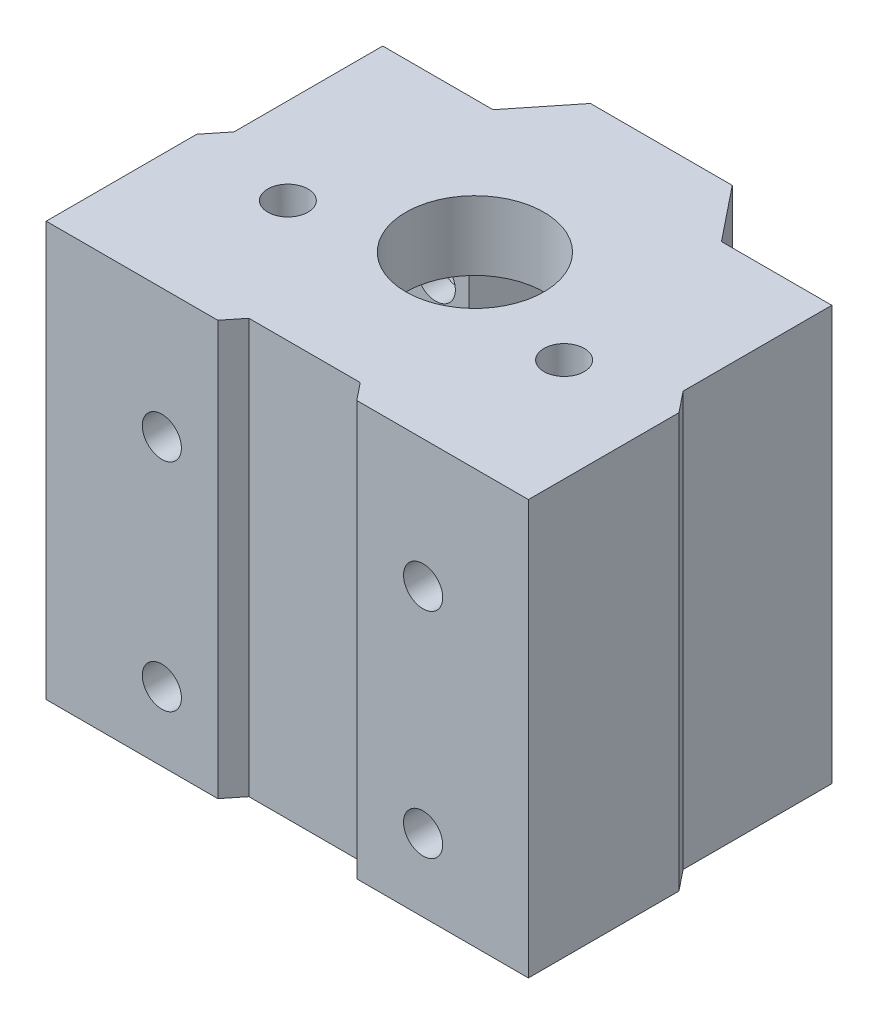
SolidWorks part; units mm, degrees
note: The reader was unsure of these and kept them because the rebuilt part matched: shared geometry of "Sketch2<3>".
ref_plane "Front Plane" through (0, 0, 0) normal (0, 0, 1) x (1, 0, 0)
ref_plane "Top Plane" through (0, 0, 0) normal (0, 1, 0) x (1, 0, 0)
ref_plane "Right Plane" through (0, 0, 0) normal (1, 0, 0) x (0, 0, -1)
sketch "Sketch1" plane through (0, 0, 0) normal (0, 1, 0) x (1, 0, 0)
  line L0 (-22.4581, 3.168) -> (18.1635, 3.168) construction
  line L19 (-4, 11.7) -> (4, 11.7)
  line L20 (4, 11.7) -> (7.76, 7)
  line L21 (7.76, 7) -> (15.01, 7)
  line L22 (15.01, 7) -> (15.01, -3)
  line L23 (15.01, -3) -> (16.45, -4.8)
  line L24 (16.45, -4.8) -> (16.45, -11.8)
  line L25 (16.45, -11.8) -> (8.2, -11.8)
  line L26 (8.2, -11.8) -> (7, -10.3)
  line L27 (7, -10.3) -> (-7, -10.3)
  line L28 (0, 11.7) -> (0, -10.3) construction
  line L29 (-8.2, -11.8) -> (-7, -10.3)
  line L30 (-16.45, -11.8) -> (-8.2, -11.8)
  line L31 (-15.01, 7) -> (-15.01, -3)
  line L32 (-16.45, -4.8) -> (-16.45, -11.8)
  line L33 (-15.01, -3) -> (-16.45, -4.8)
  line L34 (-7.76, 7) -> (-15.01, 7)
  line L35 (-4, 11.7) -> (-7.76, 7)
  circle A0 centre (0, 0) radius 6
  dimension "D1" = 12
  dimension "D4" = 11.7
  dimension "D3" = 10.3
  dimension "D13" = 4
  dimension "D15" = 7.25
  dimension "D16" = 10
  dimension "D17" = 7
  dimension "D18" = 8.25
  dimension "D19" = 7
  dimension "D20" = 22
  dimension "D21" = 23.5
  dimension "D22" = 4.7
sketch "Sketch2" plane through (0, 0, 0) normal (0, 1, 0) x (1, 0, 0)
  line L16 (-6.1628, 16.2) -> (-9.9228, 11.5)
  line L17 (-9.9228, 11.5) -> (-19.51, 11.5)
  line L18 (-19.51, 11.5) -> (-19.51, -1.4215)
  line L19 (-19.51, -1.4215) -> (-20.95, -3.2215)
  line L20 (-20.95, -3.2215) -> (-20.95, -16.3)
  line L21 (-20.95, -16.3) -> (-6.0372, -16.3)
  line L22 (-6.0372, -16.3) -> (-4.8372, -14.8)
  line L23 (-4.8372, -14.8) -> (4.8372, -14.8)
  line L24 (4.8372, -14.8) -> (6.0372, -16.3)
  line L25 (6.0372, -16.3) -> (20.95, -16.3)
  line L26 (20.95, -16.3) -> (20.95, -3.2215)
  line L27 (20.95, -3.2215) -> (19.51, -1.4215)
  line L28 (19.51, -1.4215) -> (19.51, 11.5)
  line L29 (19.51, 11.5) -> (9.9228, 11.5)
  line L30 (9.9228, 11.5) -> (6.1628, 16.2)
  line L31 (6.1628, 16.2) -> (-6.1628, 16.2)
  line L32 (-4.2403, 12.2) -> (-8.0003, 7.5)
  line L33 (-8.0003, 7.5) -> (-15.51, 7.5)
  line L34 (-15.51, 7.5) -> (-15.51, -2.8246)
  line L35 (-15.51, -2.8246) -> (-16.95, -4.6246)
  line L36 (-16.95, -4.6246) -> (-16.95, -12.3)
  line L37 (-16.95, -12.3) -> (-7.9597, -12.3)
  line L38 (-7.9597, -12.3) -> (-6.7597, -10.8)
  line L39 (-6.7597, -10.8) -> (6.7597, -10.8)
  line L40 (6.7597, -10.8) -> (7.9597, -12.3)
  line L41 (7.9597, -12.3) -> (16.95, -12.3)
  line L42 (16.95, -12.3) -> (16.95, -4.6246)
  line L43 (16.95, -4.6246) -> (15.51, -2.8246)
  line L44 (15.51, -2.8246) -> (15.51, 7.5)
  line L45 (15.51, 7.5) -> (8.0003, 7.5)
  line L46 (8.0003, 7.5) -> (4.2403, 12.2)
  line L47 (4.2403, 12.2) -> (-4.2403, 12.2)
  line L48 (-4.2403, 12.2) -> (-8.0003, 7.5)
  line L49 (-8.0003, 7.5) -> (-15.51, 7.5)
  line L50 (-15.51, 7.5) -> (-15.51, -2.8246)
  line L51 (-15.51, -2.8246) -> (-16.95, -4.6246)
  line L52 (-16.95, -4.6246) -> (-16.95, -12.3)
  line L53 (-16.95, -12.3) -> (-7.9597, -12.3)
  line L54 (-7.9597, -12.3) -> (-6.7597, -10.8)
  line L55 (-6.7597, -10.8) -> (6.7597, -10.8)
  line L56 (6.7597, -10.8) -> (7.9597, -12.3)
  line L57 (7.9597, -12.3) -> (16.95, -12.3)
  line L58 (16.95, -12.3) -> (16.95, -4.6246)
  line L59 (16.95, -4.6246) -> (15.51, -2.8246)
  line L60 (15.51, -2.8246) -> (15.51, 7.5)
  line L61 (15.51, 7.5) -> (8.0003, 7.5)
  line L62 (8.0003, 7.5) -> (4.2403, 12.2)
  line L63 (4.2403, 12.2) -> (-4.2403, 12.2)
  circle A0 centre (0, 0) radius 6 construction
  circle A1 centre (0, 0) radius 6
  dimension "D1" = 0.5
  dimension "D2" = 4
extrude "Boss-Extrude1" add sketch "Sketch2" along normal blind 6 contours A1 | L16 L17 L18 L19 L20 L21 L22 L23 L24 L25 L26 L27 L28 L29 L30 L31
extrude "Boss-Extrude2" add sketch "Sketch2<3>" against normal blind 30 contours L30 L31 L16 L17 L18 L19 L20 L21 L22 L23 L24 L25 L26 L27 L28 L29 L63 L62 L61 L60 L59 L58 L57 L56 L55 L54 L53 L52 L51 L50 L49 L48
sketch "Sketch2<3>" plane through (0, 0, 0) normal (0, 1, 0) x (1, 0, 0) same geometry as "Sketch2"
sketch "Sketch3" plane through (0, 0, 12.3) normal (0, 0, -1) x (-1, 0, 0)
  line L2 (-16.95, -30) -> (-16.95, 0) construction
  line L3 (-7.9597, -30) -> (-16.95, -30) construction
  circle A0 centre (10.9, -5.2) radius 1.7
  circle A1 centre (10.9, -24) radius 1.7
  circle A2 centre (-11.8, -23.7) radius 1.7
  circle A3 centre (-11.8, -5.1) radius 1.7
  dimension "D1" = 3.4
  dimension "D2" = 22.7
  dimension "D3" = 18.5
  dimension "D4" = 18.6
  dimension "D5" = 0.3
  dimension "D6" = 5.15
  dimension "D7" = 6.3
extrude "Cut-Extrude1" cut sketch "Sketch3" against normal through all both and the other way through all
sketch "Sketch4" plane through (0, 0, -11.5) normal (0, 0, -1) x (-1, 0, 0)
  arc A2 (-9.05, -5.1) -> (-9.05, -5.1) centre (-11.8, -5.1) ccw
  circle A3 centre (-11.8, -5.1) radius 2.75
  arc A5 (9.3193, -7.4503) -> (9.3193, -2.9497) centre (10.9, -5.2) ccw
  circle A6 centre (10.9, -5.2) radius 2.75
  arc A8 (-9.05, -23.7) -> (-9.05, -23.7) centre (-11.8, -23.7) ccw
  circle A9 centre (-11.8, -23.7) radius 2.75
  arc A11 (9.3193, -26.2503) -> (9.3193, -21.7497) centre (10.9, -24) ccw
  circle A12 centre (10.9, -24) radius 2.75
  dimension "D1" = 1.05
  dimension "D2" = 1.05
  dimension "D3" = 1.05
  dimension "D4" = 1.05
extrude "Cut-Extrude2" cut sketch "Sketch4" against normal blind 2 and the other way blind 10 draft 11
sketch "Sketch6" plane through (0, 6, 0) normal (0, 1, 0) x (1, 0, 0)
  line L0 (-12, -6) -> (0, -6) construction
  line L1 (0, -6) -> (12, -6) construction
  circle A0 centre (-12, -4.25) radius 1.75
  circle A1 centre (12, -4.25) radius 1.75
  circle A2 centre (0, 0) radius 6 construction
  dimension "D1" = 3.5
  dimension "D2" = 3.5
  dimension "D3" = 12
  dimension "D4" = 12
extrude "Cut-Extrude3" cut sketch "Sketch6" against normal through all both and the other way through all
sketch "Sketch7" plane through (0, 0, 0) normal (0, -1, 0) x (1, 0, 0)
  circle A4 centre (-12, 4.25) radius 3.25
  circle A5 centre (-12, 4.25) radius 3.25
  circle A7 centre (12, 4.25) radius 3.25
  circle A8 centre (12, 4.25) radius 3.25
  dimension "D1" = 1.5
  dimension "D2" = 1.5
extrude "Cut-Extrude4" cut sketch "Sketch7" against normal blind 2
